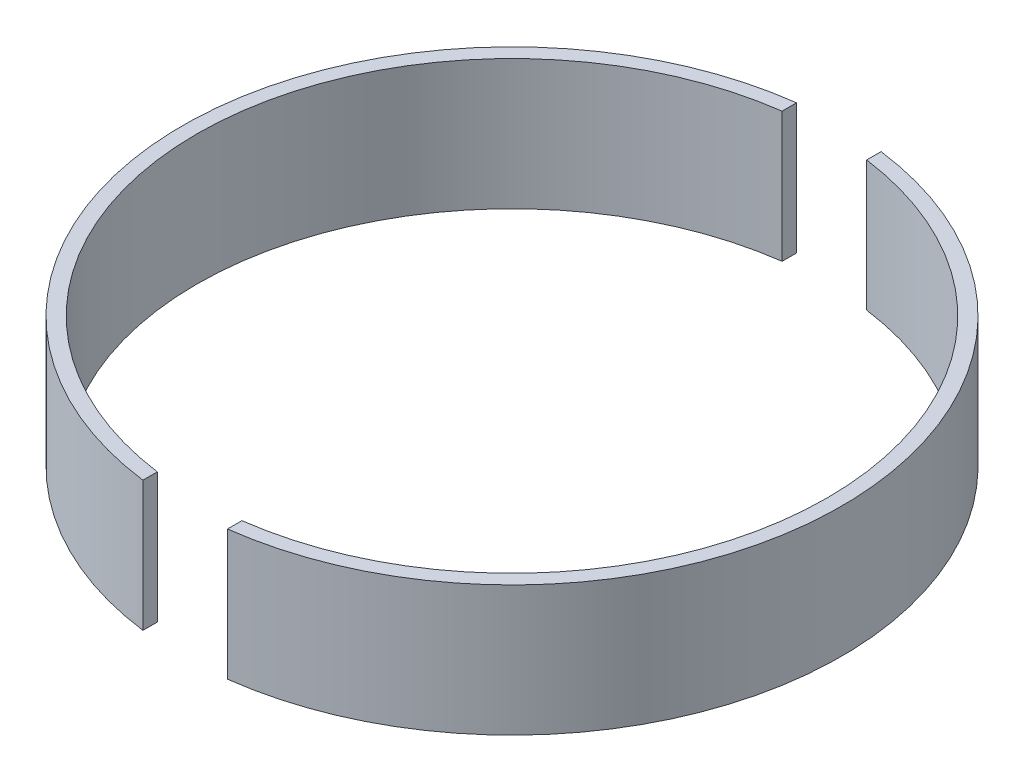
SolidWorks part; units mm, degrees
material "Thornel Mat VMA"
ref_plane "Plan de face" through (0, 0, 0) normal (0, 0, 1) x (1, 0, 0)
ref_plane "Plan de dessus" through (0, 0, 0) normal (0, 1, 0) x (1, 0, 0)
ref_plane "Plan de droite" through (0, 0, 0) normal (1, 0, 0) x (0, 0, -1)
sketch "Esquisse1" plane through (0, 0, 0) normal (0, 1, 0) x (1, 0, 0)
  circle A0 centre (0, 0) radius 76
  circle A1 centre (0, 0) radius 72.7
  dimension "D1" = 152
  dimension "D2" = 3.3
extrude "Boss.-Extru.1" add sketch "Esquisse1" along normal blind 30
ref_plane "Plan1" through (0, 15, 0) normal (0, -1, 0) x (-1, 0, 0)
sketch "Esquisse2" plane through (0, 0, 0) normal (0, -1, 0) x (1, 0, 0)
  line L2 (9.75, 99.295) -> (-9.75, 99.295)
  line L3 (9.75, 99.295) -> (9.75, -93.9769)
  line L4 (9.75, -93.9769) -> (-9.75, -93.9769)
  line L5 (-9.75, 99.295) -> (-9.75, -93.9769)
  dimension "D1" = 19.5
  dimension "D2" = 9.75
extrude "Enlèv. mat.-Extru.1" cut sketch "Esquisse2" against normal through all
